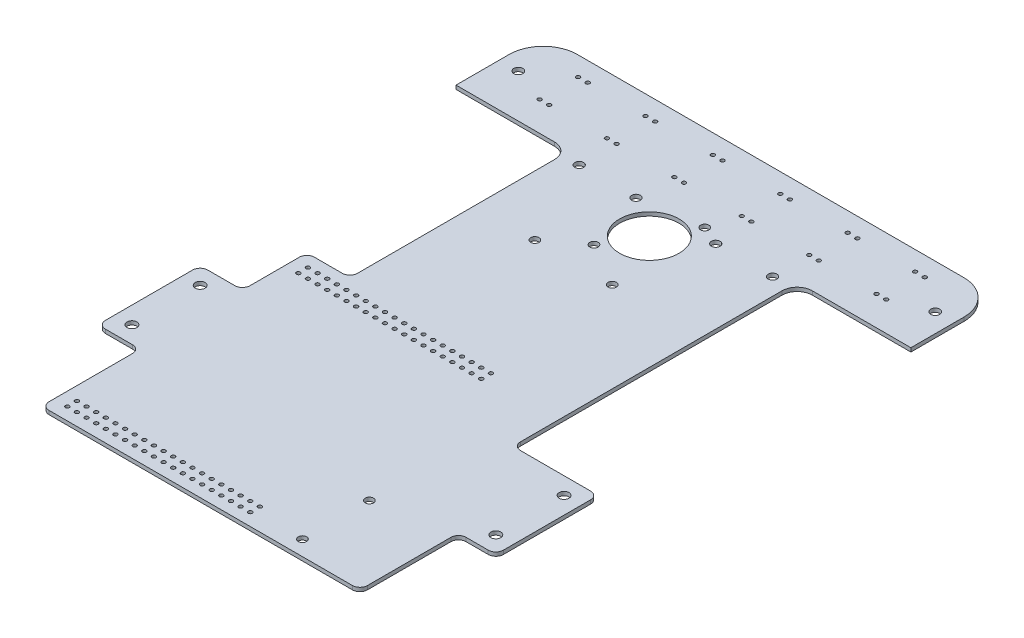
SolidWorks part; units mm, degrees
material "Thornel VCB-20 Carbon Cloth"
ref_plane "Front" through (0, 0, 0) normal (0, 0, 1) x (1, 0, 0)
ref_plane "Top" through (0, 0, 0) normal (0, 1, 0) x (1, 0, 0)
ref_plane "Right" through (0, 0, 0) normal (1, 0, 0) x (0, 0, -1)
ref_axis "X" through (-80.9, 0, 0) along (1, 0, 0)
ref_axis "Y" through (0, -50, 0) along (0, 1, 0)
ref_axis "Z" through (0, 0, -80.9) along (0, 0, 1)
sketch "Sketch1" plane through (0, 0, 0) normal (0, 1, 0) x (1, 0, 0)
  line L0 (-52.5, -125) -> (-41.35, -125)
  line L1 (-52.5, -125) -> (-52.5, -98)
  line L2 (-52.5, -98) -> (-41.35, -98)
  line L3 (-30, -81) -> (-30, -23)
  line L4 (-30, -23) -> (-60, -23)
  line L5 (-60, -23) -> (-60, 0)
  line L6 (-60, 0) -> (60, 0)
  line L7 (60, 0) -> (60, -23)
  line L8 (60, -23) -> (30, -23)
  line L9 (30, -23) -> (30, -98)
  line L10 (30, -98) -> (52.5, -98)
  line L11 (52.5, -98) -> (52.5, -125)
  line L12 (0, -162) -> (0, 0) construction
  line L13 (-41.35, -125) -> (-41.35, -151)
  line L14 (-41.35, -151) -> (42.65, -151)
  line L15 (42.65, -151) -> (42.65, -125)
  line L16 (42.65, -125) -> (52.5, -125)
  line L18 (-41.35, -98) -> (-41.35, -81)
  line L19 (-41.35, -81) -> (-30, -81)
  dimension "D1" = 105
  dimension "D2" = 60
  dimension "D3" = 27
  dimension "D4" = 90
  dimension "D5" = 23
  dimension "D6" = 120
  dimension "D7" = 125
  dimension "D8" = 41.35
  dimension "D9" = 26
  dimension "D10" = 42.65
  dimension "D11" = 17
extrude "Boss-Extrude1" add sketch "Sketch1" along normal mid plane 1
hole_wizard "M2 Clearance Hole1" positions "Sketch2" profile "Sketch3" hole size "M2" standard "ANSI Metric" end condition up to next
sketch "Sketch2" plane through (0, 0.5, 0) normal (0, 1, 0) x (1, 0, 0)
  line L0 (-48, -120.5) -> (48, -120.5) construction
  line L2 (-52.5, -125) -> (-41.35, -125) construction
  line L3 (-52.5, -98) -> (-52.5, -125) construction
  line L4 (52.5, -125) -> (52.5, -98) construction
  line L5 (-48, -102.5) -> (-48, -120.5) construction
  line L8 (48, -102.5) -> (48, -120.5) construction
  point P0 (-48, -120.5)
  point P2 (48, -120.5)
  point P15 (-48, -102.5)
  point P17 (48, -102.5)
  dimension "D1" = 4.5
  dimension "D2" = 4.5
  dimension "D3" = 4.5
  dimension "D4" = 18
sketch "Sketch3" plane through (-48, 0.5, 120.5) normal (1, 0, 0) x (0, 0, 1)
  line L0 (0, 0) -> (0, 1)
  line L1 (0, 1) -> (1.3, 1)
  line L2 (1.3, 1) -> (1.3, 0)
  line L5 (1.3, 0) -> (0, 0)
  line L11 (0, -6.35) -> (0, 107.95) construction
  dimension "Thru Hole Dia." = 2.6
  dimension "Thru Hole Depth" = 1
fillet "Fillet1" radius 2 7 edges at (-52.5, 0, 125) (52.5, 0, 98) (-52.5, 0, 98) (-41.35, 0, 151) (42.65, 0, 151) (52.5, 0, 125) (-41.35, 0, 81)
fillet "Fillet2" radius 9 2 edges at (60, 0, 0) (-60, 0, 0)
hole_wizard "M2 Clearance Hole2" positions "Sketch7" profile "Sketch8" hole size "M2" standard "ANSI Metric" end condition up to next
sketch "Sketch7" plane through (0, 0.5, 0) normal (0, 1, 0) x (1, 0, 0)
  line L0 (-55, -11.57) -> (55, -11.57) construction
  line L2 (0, 0) -> (0, -11.57) construction
  line L3 (51, 0) -> (-51, 0) construction
  line L5 (-60, -23) -> (-30, -23) construction
  point P0 (-55, -11.57)
  point P2 (55, -11.57)
  dimension "D1" = 110
  dimension "D2" = 11.43
sketch "Sketch8" plane through (-55, 0.5, 11.57) normal (1, 0, 0) x (0, 0, 1)
  line L0 (0, 0) -> (0, 1)
  line L1 (0, 1) -> (1.2, 1)
  line L2 (1.2, 1) -> (1.2, 0)
  line L5 (1.2, 0) -> (0, 0)
  line L11 (0, -6.35) -> (0, 107.95) construction
  dimension "Thru Hole Dia." = 2.4
  dimension "Thru Hole Depth" = 1
fillet "Fillet4" radius 2 5 edges at (30, 0, 98) (42.65, 0, 125) (-41.35, 0, 125) (-30, 0, 81) (-41.35, 0, 98)
fillet "Fillet5" radius 4 2 edges at (30, 0, 23) (-30, 0, 23)
sketch "Sketch13" plane through (0, 0.5, 0) normal (0, 1, 0) x (1, 0, 0)
  line L0 (-38, -106) -> (-38, -117) construction
  line L1 (-35, -106) -> (-35, -117)
  line L3 (38, -106) -> (38, -117) construction
  line L5 (35, -106) -> (35, -117)
  line L6 (-38, -111.5) -> (38, -111.5) construction
  line L7 (0, -111.5) -> (0, 0) construction
  line L8 (51, 0) -> (-51, 0) construction
  line L11 (-48, -102.5) -> (-48, -120.5) construction
  line L12 (-48, -111.5) -> (-38, -111.5) construction
  line L13 (-38, -103) -> (-45.5, -103)
  line L14 (-38, -120) -> (-45.5, -120)
  line L15 (38, -103) -> (45.5, -103)
  line L16 (38, -120) -> (45.5, -120)
  line L17 (48.5, -106) -> (48.5, -117)
  line L18 (-48.5, -106) -> (-48.5, -117)
  line L19 (-35, -111.5) -> (-48.5, -111.5) construction
  line L20 (35, -111.5) -> (48.5, -111.5) construction
  arc A0 (-35, -106) -> (-38, -103) centre (-38, -106) ccw
  arc A1 (-38, -120) -> (-35, -117) centre (-38, -117) ccw
  arc A2 (38, -103) -> (35, -106) centre (38, -106) ccw
  arc A3 (35, -117) -> (38, -120) centre (38, -117) ccw
  circle A4 centre (-48, -102.5) radius 1.3 construction
  arc A5 (45.5, -103) -> (48.5, -106) centre (45.5, -106) cw
  arc A6 (48.5, -117) -> (45.5, -120) centre (45.5, -117) cw
  arc A7 (-45.5, -103) -> (-48.5, -106) centre (-45.5, -106) ccw
  arc A8 (-48.5, -117) -> (-45.5, -120) centre (-45.5, -117) ccw
  point P2 (-38, -111.5)
  point P8 (38, -111.5)
  dimension "D5" = 3.5
  dimension "D1" = 17
  dimension "D2" = 13.5
  dimension "D3" = 70
extrude "Cut-Extrude4" [suppressed] cut sketch "Sketch13" against normal through all
hole_wizard "M2 Clearance Hole3" positions "Sketch14" profile "Sketch15" hole size "M2" standard "ANSI Metric" end condition up to next
sketch "Sketch14" plane through (0, 0.5, 0) normal (0, 1, 0) x (1, 0, 0)
  line L2 (5.35, -22.7335) -> (-5.35, -41.2665) construction
  line L3 (0, 0) -> (0, -32) construction
  line L4 (51, 0) -> (-51, 0) construction
  point P0 (5.35, -22.7335)
  point P2 (-5.35, -41.2665)
  dimension "D1" = 21.4
  dimension "D2" = 32
  dimension "D3" = 30
sketch "Sketch15" plane through (5.35, 0.5, 22.7335) normal (1, 0, 0) x (0, 0, 1)
  line L0 (0, 0) -> (0, 1)
  line L1 (0, 1) -> (1.1, 1)
  line L2 (1.1, 1) -> (1.1, 0)
  line L5 (1.1, 0) -> (0, 0)
  line L11 (0, -6.35) -> (0, 107.95) construction
  dimension "Thru Hole Dia." = 2.2
  dimension "Thru Hole Depth" = 1
sketch "Sketch17" plane through (0, 0.5, 0) normal (0, 1, 0) x (1, 0, 0)
  line L0 (-25.5, -25) -> (-10.5, -25) construction
  line L1 (-10.5, -25) -> (10.5, -25) construction
  line L2 (10.5, -25) -> (25.5, -25) construction
  line L4 (0, -25) -> (0, 0) construction
  line L5 (-18, -25) -> (-18, -29.652) construction
  line L7 (51, 0) -> (-51, 0) construction
  line L8 (18, -25) -> (18, -28.4507) construction
  circle A8 centre (25.5, -25) radius 1.15
  circle A9 centre (10.5, -25) radius 1.15
  circle A10 centre (-10.5, -25) radius 1.15
  circle A11 centre (-25.5, -25) radius 1.15
  dimension "D7" = 2.3
  dimension "D1" = 15
  dimension "D2" = 36
  dimension "D4" = 25
extrude "Cut-Extrude6" cut sketch "Sketch17" against normal through all
sketch "Sketch18" plane through (0, 0.5, 0) normal (0, 1, 0) x (1, 0, 0)
  line L0 (5.35, -22.7335) -> (-5.35, -41.2665) construction
  circle A0 centre (0, -32) radius 7.85
  circle A6 centre (5.35, -22.7335) radius 1.1 construction
  circle A8 centre (-5.35, -41.2665) radius 1.1 construction
  dimension "D3" = 15.7
extrude "Cut-Extrude7" cut sketch "Sketch18" against normal up to next
hole_wizard "M2 Clearance Hole4" positions "Sketch19" profile "Sketch20" hole size "M2" standard "ANSI Metric" end condition up to next
sketch "Sketch19" plane through (0, 0.5, 0) normal (0, 1, 0) x (1, 0, 0)
  line L0 (-14.21, -48) -> (6.21, -48) construction
  line L2 (0, 0) -> (0, -48) construction
  line L3 (51, 0) -> (-51, 0) construction
  point P0 (-14.21, -48)
  point P2 (6.21, -48)
  dimension "D1" = 20.42
  dimension "D2" = 6.21
  dimension "D3" = 48
sketch "Sketch20" plane through (-14.21, 0.5, 48) normal (1, 0, 0) x (0, 0, 1)
  line L0 (0, 0) -> (0, 1)
  line L1 (0, 1) -> (1.1, 1)
  line L2 (1.1, 1) -> (1.1, 0)
  line L5 (1.1, 0) -> (0, 0)
  line L11 (0, -6.35) -> (0, 107.95) construction
  dimension "Thru Hole Dia." = 2.2
  dimension "Thru Hole Depth" = 1
sketch "Sketch21" plane through (0, 0.5, 0) normal (0, 1, 0) x (1, 0, 0)
  line L0 (-37.826, -86.7798) -> (-37.826, -147.73) construction
  line L4 (-39.35, -151) -> (40.65, -151) construction
  line L5 (-41.35, -127) -> (-41.35, -149) construction
  circle A0 centre (-37.826, -147.73) radius 0.51
  circle A2 centre (-37.826, -86.7798) radius 0.51
  dimension "D2" = 1.02
  dimension "D3" = 3.524
  dimension "D4" = 3.27
  dimension "D1" = 60.9502
extrude "Cut-Extrude8" cut sketch "Sketch21" against normal up to next
pattern_linear "LPattern1" count 2 spacing 2.54 along (0, 0, -1) count 20 spacing 2.54 along (1, 0, 0) of "Cut-Extrude8"
sketch "Sketch22" plane through (0, 0.5, 0) normal (0, 1, 0) x (1, 0, 0)
  line L0 (-45.72, -5.08) -> (-43.18, -5.08) construction
  line L1 (51, 0) -> (-51, 0) construction
  line L2 (-44.45, -5.08) -> (-44.45, 0) construction
  circle A0 centre (-45.72, -5.08) radius 0.51
  circle A1 centre (-43.18, -5.08) radius 0.51
  point P8 (0, 0)
  dimension "D2" = 1.02
  dimension "D1" = 2.54
  dimension "D3" = 5.08
  dimension "D4" = 44.45
extrude "Cut-Extrude9" cut sketch "Sketch22" against normal up to next
pattern_linear "LPattern2" count 2 spacing 10.16 along (0, 0, 1) count 6 spacing 17.78 along (1, 0, 0) of "Cut-Extrude9"
sketch "Sketch23" plane through (0, 0.5, 0) normal (0, 1, 0) x (1, 0, 0)
  line L0 (42.65, -149) -> (42.65, -127) construction
  line L1 (-39.35, -151) -> (40.65, -151) construction
  circle A0 centre (23.48, -147) radius 1.1
  circle A1 centre (23.48, -129.35) radius 1.1
  point P4 (0, 0)
  dimension "D1" = 2.2
  dimension "D2" = 17.65
  dimension "D3" = 19.17
  dimension "D4" = 4
extrude "Cut-Extrude10" cut sketch "Sketch23" against normal through all
equation "\"dd\"=4"
